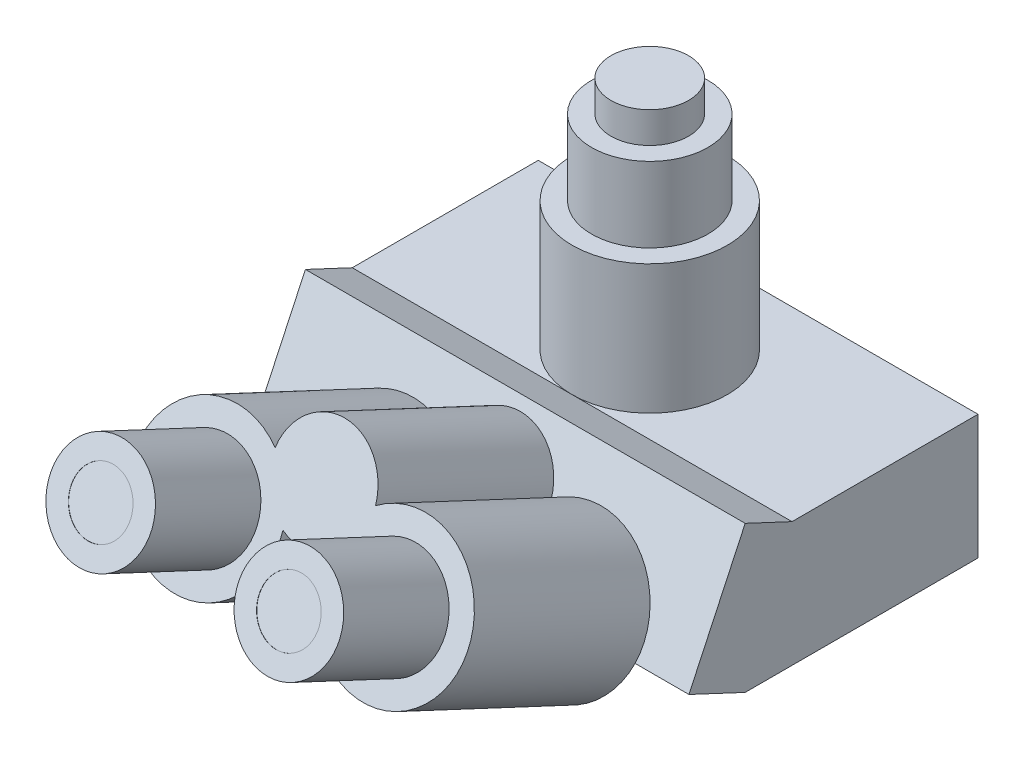
SolidWorks part; units mm, degrees
ref_plane "Front Plane" through (0, 0, 0) normal (0, 0, 1) x (1, 0, 0)
ref_plane "Top Plane" through (0, 0, 0) normal (0, 1, 0) x (1, 0, 0)
ref_plane "Right Plane" through (0, 0, 0) normal (1, 0, 0) x (0, 0, -1)
sketch "Sketch3" plane through (0, 0, 0) normal (1, 0, 0) x (0, 0, -1)
  line L0 (0, 0) -> (90, 0)
  line L1 (90, 0) -> (90, 48.125)
  line L2 (90, 48.125) -> (18.1133, 48.125)
  line L3 (18.1133, 48.125) -> (0, 56.6048)
  line L4 (0, 56.6048) -> (-21.736, 10.1758)
  line L5 (-21.736, 10.1758) -> (0, 0)
  dimension "D1" = 90
  dimension "D2" = 48.125
  dimension "D3" = 24
  dimension "D4" = 20
extrude "Boss-Extrude1" add sketch "Sketch3" along normal mid plane 170
sketch "Sketch4" plane through (0, 48.125, 0) normal (0, 1, 0) x (1, 0, 0)
  line L0 (85, 18.1133) -> (-85, 18.1133) construction
  circle A0 centre (0, 48.1133) radius 30
  dimension "D1" = 60
extrude "Boss-Extrude2" add sketch "Sketch4" along normal blind 50
sketch "Sketch5" plane through (0, 98.125, 0) normal (0, 1, 0) x (1, 0, 0)
  circle A0 centre (0, 48.1133) radius 22.5
  circle A1 centre (0, 48.1133) radius 30 construction
  dimension "D1" = 45
extrude "Boss-Extrude3" add sketch "Sketch5" along normal blind 29
sketch "Sketch6" plane through (0, 127.125, 0) normal (0, 1, 0) x (1, 0, 0)
  circle A0 centre (0, 48.1133) radius 15
  circle A1 centre (0, 48.1133) radius 22.5 construction
  dimension "D1" = 30
extrude "Boss-Extrude4" add sketch "Sketch6" along normal blind 12
sketch "Sketch7" plane through (0, 10.1758, 21.736) normal (0, 0.424, 0.9057) x (1, 0, 0)
  line L0 (0, -972.7349) -> (0, 49027.2651) construction
  line L1 (0, 27.2651) -> (36.3731, 6.2651) construction
  line L2 (0, 27.2651) -> (-36.3731, 6.2651) construction
  line L3 (85, 51.2651) -> (-85, 51.2651) construction
  arc A0 (-8.0582, 9.5079) -> (8.0582, 9.5079) centre (0, 27.2651) ccw
  arc A1 (8.0582, 9.5079) -> (19.4072, 29.1651) centre (36.3731, 6.2651) ccw
  arc A2 (-19.4072, 29.1651) -> (-8.0582, 9.5079) centre (-36.3731, 6.2651) ccw
  arc A3 (-11.6913, 20.5151) -> (-19.4072, 29.1651) centre (-36.3731, 6.2651) ccw construction
  arc A4 (-19.4072, 29.1651) -> (-16.8875, 17.5151) centre (0, 27.2651) ccw construction
  arc A5 (-16.8875, 17.5151) -> (-8.0582, 9.5079) centre (0, 27.2651) ccw construction
  arc A6 (-8.0582, 9.5079) -> (-11.6913, 20.5151) centre (-36.3731, 6.2651) ccw construction
  arc A7 (16.8875, 17.5151) -> (19.4072, 29.1651) centre (0, 27.2651) ccw construction
  arc A8 (19.4072, 29.1651) -> (-19.4072, 29.1651) centre (0, 27.2651) ccw
  arc A9 (19.4072, 29.1651) -> (11.6913, 20.5151) centre (36.3731, 6.2651) ccw construction
  arc A10 (11.6913, 20.5151) -> (8.0582, 9.5079) centre (36.3731, 6.2651) ccw construction
  arc A11 (8.0582, 9.5079) -> (16.8875, 17.5151) centre (0, 27.2651) ccw construction
  point P11 (0, 0)
  dimension "D4" = 39
  dimension "D5" = 57
  dimension "D6" = 42
  dimension "D1" = 60
  dimension "D2" = 60
  dimension "D3" = 24
extrude "Boss-Extrude5" add sketch "Sketch7" along normal blind 75
ref_axis "Axis light should pass through" through (0, 98.125, -48.1133) along (0, -1, 0)
sketch "Sketch8" plane through (0, 41.9752, 89.6609) normal (0, 0.424, 0.9057) x (1, 0, 0)
  circle A0 centre (-36.3731, 6.2651) radius 19.5
  circle A1 centre (36.3731, 6.2651) radius 19.5
  arc A2 (-19.4072, 29.1651) -> (-64.1759, 0) centre (-36.3731, 6.2651) ccw construction
  arc A3 (8.0582, 9.5079) -> (19.4072, 29.1651) centre (36.3731, 6.2651) ccw construction
  dimension "D1" = 39
extrude "Boss-Extrude6" add sketch "Sketch8" along normal blind 45
sketch "Sketch9" plane through (0, 61.0548, 130.4159) normal (0, 0.424, 0.9057) x (1, 0, 0)
  circle A0 centre (-36.3731, 6.2651) radius 11.5
  circle A1 centre (36.3731, 6.2651) radius 11.5
  circle A2 centre (36.3731, 6.2651) radius 19.5 construction
  circle A3 centre (-36.3731, 6.2651) radius 19.5 construction
  point P10 (0, 0)
  dimension "D1" = 23
extrude "Cut-Extrude1" cut sketch "Sketch9" against normal blind 0.1
